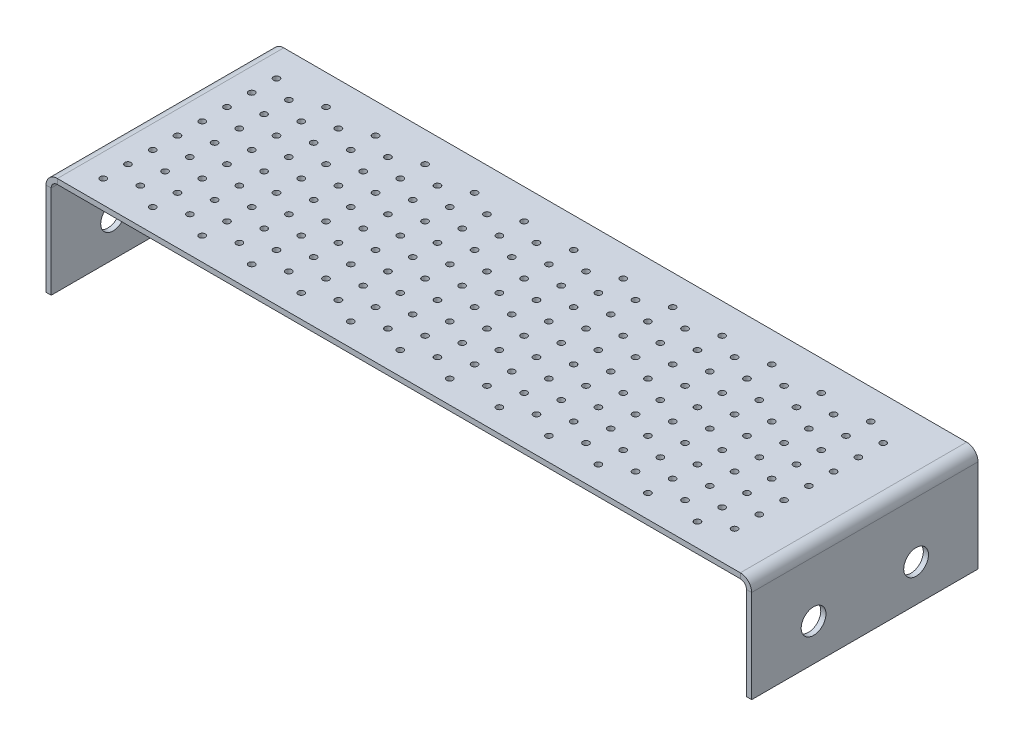
SolidWorks part; units mm, degrees
note: The reader was unsure of these and kept them because the rebuilt part matched: flange length of "Edge-Flange1", "Edge-Flange2".
material "Plain Carbon Steel"
ref_plane "Front Plane" through (0, 0, 0) normal (0, 0, 1) x (1, 0, 0)
ref_plane "Top Plane" through (0, 0, 0) normal (0, 1, 0) x (1, 0, 0)
ref_plane "Right Plane" through (0, 0, 0) normal (1, 0, 0) x (0, 0, -1)
sketch "Sketch1" plane through (0, 0, 0) normal (0, 1, 0) x (1, 0, 0)
  line L1 (0, 0) -> (361.95, 0)
  line L2 (0, 0) -> (0, 116.0882)
  line L3 (0, 116.0882) -> (361.95, 116.0882)
  line L4 (361.95, 0) -> (361.95, 116.0882)
  dimension "D1" = 361.95
  dimension "D2" = 116.0882
base flange "Base-Flange1" sketch "Sketch1" thickness 2.6568 reverse thickness direction no parameters "D1"=3.175
edge flange "Edge-Flange1" sketch "Sketch8" flange angle 90 flange length 50.8 flange position material inside bend radius 3.175 thickness 2.6568 relief rectangular parameters "D6"=10
sketch "Sketch8" plane through (361.95, -2.6568, 0) normal (-1, 0, 0) x (0, 0, -1)
  line L2 (0, 0) -> (0, 50.8)
  line L3 (0, 50.8) -> (116.0882, 50.8)
  line L4 (116.0882, 50.8) -> (116.0882, 0)
  line L5 (116.0882, 0) -> (0, 0) construction
  line L6 (116.0882, 0) -> (0, 0)
bend "EdgeBend1" bend radius 3.175 bend angle 90 parameters "D5"=1
edge flange "Edge-Flange2" sketch "Sketch11" flange angle 90 flange length 50.8 flange position material inside bend radius 3.175 thickness 2.6568 relief rectangular parameters "D6"=10
sketch "Sketch11" plane through (0, -2.6568, 0) normal (1, 0, 0) x (0, 0, 1)
  line L2 (-116.0882, 0) -> (-116.0882, 50.8)
  line L3 (-116.0882, 50.8) -> (0, 50.8)
  line L4 (0, 50.8) -> (0, 0)
  line L5 (0, 0) -> (-116.0882, 0) construction
  line L6 (0, 0) -> (-116.0882, 0)
bend "EdgeBend2" bend radius 3.175 bend angle 90 parameters "D5"=2
sketch "Sketch12" plane through (0, 0, 0) normal (0, 1, 0) x (1, 0, 0)
  line L0 (5.8318, 116.0882) -> (5.8318, 0) construction
  line L1 (15.9918, 105.9282) -> (345.9582, 105.9282) construction
  line L2 (15.9918, 105.9282) -> (15.9918, 10.16) construction
  line L3 (15.9918, 10.16) -> (345.9582, 10.16) construction
  line L4 (345.9582, 105.9282) -> (345.9582, 10.16) construction
  line L5 (356.1182, 116.0882) -> (5.8318, 116.0882) construction
  line L6 (5.8318, 0) -> (356.1182, 0) construction
  line L7 (356.1182, 0) -> (356.1182, 116.0882) construction
  line L8 (17.5793, 11.7475) -> (17.5793, 24.4475) construction
  line L9 (17.5793, 11.7475) -> (17.5793, 14.9225) construction
  line L10 (17.5793, 11.7475) -> (42.9793, 11.7475) construction
  line L11 (30.2793, 18.0975) -> (30.2793, 30.7975) construction
  line L12 (30.2793, 43.4975) -> (55.6793, 43.4975) construction
  circle A0 centre (17.5793, 11.7475) radius 1.5875
  circle A1 centre (17.5793, 24.4475) radius 1.5875
  circle A2 centre (17.5793, 37.1475) radius 1.5875
  circle A3 centre (17.5793, 49.8475) radius 1.5875
  circle A4 centre (17.5793, 62.5475) radius 1.5875
  circle A5 centre (17.5793, 75.2475) radius 1.5875
  circle A6 centre (17.5793, 87.9475) radius 1.5875
  circle A7 centre (17.5793, 100.6475) radius 1.5875
  circle A8 centre (42.9793, 11.7475) radius 1.5875
  circle A9 centre (42.9793, 24.4475) radius 1.5875
  circle A10 centre (42.9793, 37.1475) radius 1.5875
  circle A11 centre (42.9793, 49.8475) radius 1.5875
  circle A12 centre (42.9793, 62.5475) radius 1.5875
  circle A13 centre (42.9793, 75.2475) radius 1.5875
  circle A14 centre (42.9793, 87.9475) radius 1.5875
  circle A15 centre (42.9793, 100.6475) radius 1.5875
  circle A16 centre (68.3793, 11.7475) radius 1.5875
  circle A17 centre (68.3793, 24.4475) radius 1.5875
  circle A18 centre (68.3793, 37.1475) radius 1.5875
  circle A19 centre (68.3793, 49.8475) radius 1.5875
  circle A20 centre (68.3793, 62.5475) radius 1.5875
  circle A21 centre (68.3793, 75.2475) radius 1.5875
  circle A22 centre (68.3793, 87.9475) radius 1.5875
  circle A23 centre (68.3793, 100.6475) radius 1.5875
  circle A24 centre (93.7793, 11.7475) radius 1.5875
  circle A25 centre (93.7793, 24.4475) radius 1.5875
  circle A26 centre (93.7793, 37.1475) radius 1.5875
  circle A27 centre (93.7793, 49.8475) radius 1.5875
  circle A28 centre (93.7793, 62.5475) radius 1.5875
  circle A29 centre (93.7793, 75.2475) radius 1.5875
  circle A30 centre (93.7793, 87.9475) radius 1.5875
  circle A31 centre (93.7793, 100.6475) radius 1.5875
  circle A32 centre (119.1793, 11.7475) radius 1.5875
  circle A33 centre (119.1793, 24.4475) radius 1.5875
  circle A34 centre (119.1793, 37.1475) radius 1.5875
  circle A35 centre (119.1793, 49.8475) radius 1.5875
  circle A36 centre (119.1793, 62.5475) radius 1.5875
  circle A37 centre (119.1793, 75.2475) radius 1.5875
  circle A38 centre (119.1793, 87.9475) radius 1.5875
  circle A39 centre (119.1793, 100.6475) radius 1.5875
  circle A40 centre (144.5793, 11.7475) radius 1.5875
  circle A41 centre (144.5793, 24.4475) radius 1.5875
  circle A42 centre (144.5793, 37.1475) radius 1.5875
  circle A43 centre (144.5793, 49.8475) radius 1.5875
  circle A44 centre (144.5793, 62.5475) radius 1.5875
  circle A45 centre (144.5793, 75.2475) radius 1.5875
  circle A46 centre (144.5793, 87.9475) radius 1.5875
  circle A47 centre (144.5793, 100.6475) radius 1.5875
  circle A48 centre (169.9793, 11.7475) radius 1.5875
  circle A49 centre (169.9793, 24.4475) radius 1.5875
  circle A50 centre (169.9793, 37.1475) radius 1.5875
  circle A51 centre (169.9793, 49.8475) radius 1.5875
  circle A52 centre (169.9793, 62.5475) radius 1.5875
  circle A53 centre (169.9793, 75.2475) radius 1.5875
  circle A54 centre (169.9793, 87.9475) radius 1.5875
  circle A55 centre (169.9793, 100.6475) radius 1.5875
  circle A56 centre (195.3793, 11.7475) radius 1.5875
  circle A57 centre (195.3793, 24.4475) radius 1.5875
  circle A58 centre (195.3793, 37.1475) radius 1.5875
  circle A59 centre (195.3793, 49.8475) radius 1.5875
  circle A60 centre (195.3793, 62.5475) radius 1.5875
  circle A61 centre (195.3793, 75.2475) radius 1.5875
  circle A62 centre (195.3793, 87.9475) radius 1.5875
  circle A63 centre (195.3793, 100.6475) radius 1.5875
  circle A64 centre (220.7793, 11.7475) radius 1.5875
  circle A65 centre (220.7793, 24.4475) radius 1.5875
  circle A66 centre (220.7793, 37.1475) radius 1.5875
  circle A67 centre (220.7793, 49.8475) radius 1.5875
  circle A68 centre (220.7793, 62.5475) radius 1.5875
  circle A69 centre (220.7793, 75.2475) radius 1.5875
  circle A70 centre (220.7793, 87.9475) radius 1.5875
  circle A71 centre (220.7793, 100.6475) radius 1.5875
  circle A72 centre (246.1793, 11.7475) radius 1.5875
  circle A73 centre (246.1793, 24.4475) radius 1.5875
  circle A74 centre (246.1793, 37.1475) radius 1.5875
  circle A75 centre (246.1793, 49.8475) radius 1.5875
  circle A76 centre (246.1793, 62.5475) radius 1.5875
  circle A77 centre (246.1793, 75.2475) radius 1.5875
  circle A78 centre (246.1793, 87.9475) radius 1.5875
  circle A79 centre (246.1793, 100.6475) radius 1.5875
  circle A80 centre (271.5793, 11.7475) radius 1.5875
  circle A81 centre (271.5793, 24.4475) radius 1.5875
  circle A82 centre (271.5793, 37.1475) radius 1.5875
  circle A83 centre (271.5793, 49.8475) radius 1.5875
  circle A84 centre (271.5793, 62.5475) radius 1.5875
  circle A85 centre (271.5793, 75.2475) radius 1.5875
  circle A86 centre (271.5793, 87.9475) radius 1.5875
  circle A87 centre (271.5793, 100.6475) radius 1.5875
  circle A88 centre (296.9793, 11.7475) radius 1.5875
  circle A89 centre (296.9793, 24.4475) radius 1.5875
  circle A90 centre (296.9793, 37.1475) radius 1.5875
  circle A91 centre (296.9793, 49.8475) radius 1.5875
  circle A92 centre (296.9793, 62.5475) radius 1.5875
  circle A93 centre (296.9793, 75.2475) radius 1.5875
  circle A94 centre (296.9793, 87.9475) radius 1.5875
  circle A95 centre (296.9793, 100.6475) radius 1.5875
  circle A96 centre (322.3793, 11.7475) radius 1.5875
  circle A97 centre (322.3793, 24.4475) radius 1.5875
  circle A98 centre (322.3793, 37.1475) radius 1.5875
  circle A99 centre (322.3793, 49.8475) radius 1.5875
  circle A100 centre (322.3793, 62.5475) radius 1.5875
  circle A101 centre (322.3793, 75.2475) radius 1.5875
  circle A102 centre (322.3793, 87.9475) radius 1.5875
  circle A103 centre (322.3793, 100.6475) radius 1.5875
  circle A104 centre (30.2793, 18.0975) radius 1.5875
  circle A105 centre (30.2793, 30.7975) radius 1.5875
  circle A106 centre (30.2793, 43.4975) radius 1.5875
  circle A107 centre (30.2793, 56.1975) radius 1.5875
  circle A108 centre (30.2793, 68.8975) radius 1.5875
  circle A109 centre (30.2793, 81.5975) radius 1.5875
  circle A110 centre (30.2793, 94.2975) radius 1.5875
  circle A111 centre (55.6793, 43.4975) radius 1.5875
  circle A112 centre (55.6793, 56.1975) radius 1.5875
  circle A113 centre (55.6793, 68.8975) radius 1.5875
  circle A114 centre (55.6793, 81.5975) radius 1.5875
  circle A115 centre (55.6793, 94.2975) radius 1.5875
  circle A116 centre (55.6793, 30.7975) radius 1.5875
  circle A117 centre (55.6793, 18.0975) radius 1.5875
  circle A118 centre (81.0793, 43.4975) radius 1.5875
  circle A119 centre (81.0793, 56.1975) radius 1.5875
  circle A120 centre (81.0793, 68.8975) radius 1.5875
  circle A121 centre (81.0793, 81.5975) radius 1.5875
  circle A122 centre (81.0793, 94.2975) radius 1.5875
  circle A123 centre (81.0793, 30.7975) radius 1.5875
  circle A124 centre (81.0793, 18.0975) radius 1.5875
  circle A125 centre (106.4793, 43.4975) radius 1.5875
  circle A126 centre (106.4793, 56.1975) radius 1.5875
  circle A127 centre (106.4793, 68.8975) radius 1.5875
  circle A128 centre (106.4793, 81.5975) radius 1.5875
  circle A129 centre (106.4793, 94.2975) radius 1.5875
  circle A130 centre (106.4793, 30.7975) radius 1.5875
  circle A131 centre (106.4793, 18.0975) radius 1.5875
  circle A132 centre (131.8793, 43.4975) radius 1.5875
  circle A133 centre (131.8793, 56.1975) radius 1.5875
  circle A134 centre (131.8793, 68.8975) radius 1.5875
  circle A135 centre (131.8793, 81.5975) radius 1.5875
  circle A136 centre (131.8793, 94.2975) radius 1.5875
  circle A137 centre (131.8793, 30.7975) radius 1.5875
  circle A138 centre (131.8793, 18.0975) radius 1.5875
  circle A139 centre (157.2793, 43.4975) radius 1.5875
  circle A140 centre (157.2793, 56.1975) radius 1.5875
  circle A141 centre (157.2793, 68.8975) radius 1.5875
  circle A142 centre (157.2793, 81.5975) radius 1.5875
  circle A143 centre (157.2793, 94.2975) radius 1.5875
  circle A144 centre (157.2793, 30.7975) radius 1.5875
  circle A145 centre (157.2793, 18.0975) radius 1.5875
  circle A146 centre (182.6793, 43.4975) radius 1.5875
  circle A147 centre (182.6793, 56.1975) radius 1.5875
  circle A148 centre (182.6793, 68.8975) radius 1.5875
  circle A149 centre (182.6793, 81.5975) radius 1.5875
  circle A150 centre (182.6793, 94.2975) radius 1.5875
  circle A151 centre (182.6793, 30.7975) radius 1.5875
  circle A152 centre (182.6793, 18.0975) radius 1.5875
  circle A153 centre (208.0793, 43.4975) radius 1.5875
  circle A154 centre (208.0793, 56.1975) radius 1.5875
  circle A155 centre (208.0793, 68.8975) radius 1.5875
  circle A156 centre (208.0793, 81.5975) radius 1.5875
  circle A157 centre (208.0793, 94.2975) radius 1.5875
  circle A158 centre (208.0793, 30.7975) radius 1.5875
  circle A159 centre (208.0793, 18.0975) radius 1.5875
  circle A160 centre (233.4793, 43.4975) radius 1.5875
  circle A161 centre (233.4793, 56.1975) radius 1.5875
  circle A162 centre (233.4793, 68.8975) radius 1.5875
  circle A163 centre (233.4793, 81.5975) radius 1.5875
  circle A164 centre (233.4793, 94.2975) radius 1.5875
  circle A165 centre (233.4793, 30.7975) radius 1.5875
  circle A166 centre (233.4793, 18.0975) radius 1.5875
  circle A167 centre (258.8793, 43.4975) radius 1.5875
  circle A168 centre (258.8793, 56.1975) radius 1.5875
  circle A169 centre (258.8793, 68.8975) radius 1.5875
  circle A170 centre (258.8793, 81.5975) radius 1.5875
  circle A171 centre (258.8793, 94.2975) radius 1.5875
  circle A172 centre (258.8793, 30.7975) radius 1.5875
  circle A173 centre (258.8793, 18.0975) radius 1.5875
  circle A174 centre (284.2793, 43.4975) radius 1.5875
  circle A175 centre (284.2793, 56.1975) radius 1.5875
  circle A176 centre (284.2793, 68.8975) radius 1.5875
  circle A177 centre (284.2793, 81.5975) radius 1.5875
  circle A178 centre (284.2793, 94.2975) radius 1.5875
  circle A179 centre (284.2793, 30.7975) radius 1.5875
  circle A180 centre (284.2793, 18.0975) radius 1.5875
  circle A181 centre (309.6793, 43.4975) radius 1.5875
  circle A182 centre (309.6793, 56.1975) radius 1.5875
  circle A183 centre (309.6793, 68.8975) radius 1.5875
  circle A184 centre (309.6793, 81.5975) radius 1.5875
  circle A185 centre (309.6793, 94.2975) radius 1.5875
  circle A186 centre (309.6793, 30.7975) radius 1.5875
  circle A187 centre (309.6793, 18.0975) radius 1.5875
  circle A188 centre (335.0793, 43.4975) radius 1.5875
  circle A189 centre (335.0793, 56.1975) radius 1.5875
  circle A190 centre (335.0793, 68.8975) radius 1.5875
  circle A191 centre (335.0793, 81.5975) radius 1.5875
  circle A192 centre (335.0793, 94.2975) radius 1.5875
  circle A193 centre (335.0793, 30.7975) radius 1.5875
  circle A194 centre (335.0793, 18.0975) radius 1.5875
  dimension "D5" = 3.175
  dimension "D10" = 3.175
  dimension "D1" = 10.16
  dimension "D2" = 10.16
  dimension "D3" = 10.16
  dimension "D4" = 10.16
  dimension "D7" = 12.7
  dimension "D8" = 13
  dimension "D9" = 25.4
  dimension "D12" = 12.7
  dimension "D11" = 6.35
  dimension "D14" = 12.7
  dimension "D16" = 25.4
  dimension "D6" = 8
  dimension "D13" = 7
  dimension "D15" = 13
extrude "Cut-Extrude1" cut sketch "Sketch12" against normal through all normal cut yes
sketch "Sketch13" plane through (361.95, 0, 0) normal (1, 0, 0) x (0, 0, -1)
  line L0 (0, -53.4568) -> (0, -5.8318) construction
  line L1 (116.0882, -5.8318) -> (116.0882, -53.4568) construction
  line L3 (116.0882, -53.4568) -> (0, -53.4568) construction
  circle A0 centre (31.75, -34.4068) radius 6.35
  circle A1 centre (84.3382, -34.4068) radius 6.35
  dimension "D1" = 12.7
  dimension "D2" = 31.75
  dimension "D3" = 31.75
  dimension "D4" = 19.05
  dimension "D5" = 19.05
extrude "Cut-Extrude2" cut sketch "Sketch13" against normal through all both and the other way through all normal cut yes
sketch "Bend-Lines1" [suppressed] plane through (0, 0, 0) normal (0, 1, 0) x (1, 0, 0)
sketch "Bounding-Box1" [suppressed] plane through (0, 0, 0) normal (0, 1, 0) x (1, 0, 0)
sheet metal parameters "Sheet-Metal1" thickness 2.6568 parameters "D1"=3.175
flat pattern "Flat-Pattern1" [suppressed]
sketch "Bend-Lines2" plane through (0, 0, 0) normal (0, 1, 0) x (1, 0, 0)
sketch3d "Bounding-Box2" [suppressed]
  line L0 (-361.95, 119.6975, 0) -> (0, 119.6975, 0) construction
  line L1 (-361.95, 0, 0) -> (0, 0, 0) construction
  line L2 (-361.95, 119.6975, 0) -> (-361.95, 0, 0) construction
  line L3 (0, 119.6975, 0) -> (0, 0, 0) construction
sheet metal parameters "Sheet-Metal2" thickness 2.6568 parameters "D1"=3.175
flat pattern "Flat-Pattern1"
sketch "Bend-Lines2" plane through (0, 0, 0) normal (0, 1, 0) x (1, 0, 0)
  line L0 (359.6551, 0) -> (359.6551, 119.6975) construction
  line L1 (359.6551, 0) -> (359.6551, 119.6975) construction
sketch3d "Bounding-Box2" [suppressed]
  line L0 (410.8171, 119.6975, 0) -> (0, 119.6975, 0) construction
  line L1 (410.8171, 0, 0) -> (0, 0, 0) construction
  line L2 (410.8171, 119.6975, 0) -> (410.8171, 0, 0) construction
  line L3 (0, 119.6975, 0) -> (0, 0, 0) construction
bend of the flat pattern "Flatten-<EdgeBend1>1"
sheet metal parameters "Sheet-Metal3" thickness 2.6568 parameters "D1"=3.175
flat pattern "Flat-Pattern1"
sketch "Bend-Lines2" plane through (0, 0, 0) normal (0, 1, 0) x (1, 0, 0)
  line L0 (359.6551, 0) -> (359.6551, 119.38) construction
  line L1 (359.6551, 0) -> (359.6551, 119.38) construction
  line L2 (2.2949, 119.38) -> (2.2949, 0) construction
  line L3 (2.2949, 119.38) -> (2.2949, 0) construction
sketch3d "Bounding-Box2" [suppressed]
  line L0 (410.8171, 119.38, 0) -> (-48.8671, 119.38, 0) construction
  line L1 (410.8171, 0, 0) -> (-48.8671, 0, 0) construction
  line L2 (410.8171, 119.38, 0) -> (410.8171, 0, 0) construction
  line L3 (-48.8671, 119.38, 0) -> (-48.8671, 0, 0) construction
bend of the flat pattern "Flatten-<EdgeBend1>1"
bend of the flat pattern "Flatten-<EdgeBend2>1"
sheet metal parameters "Sheet-Metal4" thickness 2.6568 parameters "D1"=3.175
flat pattern "Flat-Pattern1" [suppressed]
sketch "Bend-Lines2" plane through (0, 0, 0) normal (0, 1, 0) x (1, 0, 0)
  line L0 (359.6551, 0) -> (359.6551, 119.38) construction
  line L1 (359.6551, 0) -> (359.6551, 119.38) construction
  line L2 (2.2949, 119.38) -> (2.2949, 0) construction
  line L3 (2.2949, 119.38) -> (2.2949, 0) construction
sketch3d "Bounding-Box2" [suppressed]
  line L0 (410.8171, 119.38, 0) -> (-48.8671, 119.38, 0) construction
  line L1 (410.8171, 0, 0) -> (-48.8671, 0, 0) construction
  line L2 (410.8171, 119.38, 0) -> (410.8171, 0, 0) construction
  line L3 (-48.8671, 119.38, 0) -> (-48.8671, 0, 0) construction
bend of the flat pattern "Flatten-<EdgeBend1>1"
bend of the flat pattern "Flatten-<EdgeBend2>1"
sketch "Sketch13-1" [suppressed] plane through (357.3603, -2.6568, 0) normal (0, -1, 0) x (0, 0, 1)
  circle A2 centre (-87.63, -29.6443) radius 6.35
  circle A3 centre (-31.75, -29.6443) radius 6.35
sheet metal parameters "Sheet-Metal6" thickness 2.6568 parameters "D1"=3.175
flat pattern "Flat-Pattern1"
sketch "Bend-Lines2" plane through (0, 0, 0) normal (0, 1, 0) x (1, 0, 0)
  line L0 (359.6551, 0) -> (359.6551, 116.0882) construction
  line L1 (359.6551, 0) -> (359.6551, 116.0882) construction
  line L2 (2.2949, 116.0882) -> (2.2949, 0) construction
  line L3 (2.2949, 116.0882) -> (2.2949, 0) construction
sketch3d "Bounding-Box2" [suppressed]
  line L0 (410.8171, 116.0882, 0) -> (-48.8671, 116.0882, 0) construction
  line L1 (410.8171, 0, 0) -> (-48.8671, 0, 0) construction
  line L2 (410.8171, 116.0882, 0) -> (410.8171, 0, 0) construction
  line L3 (-48.8671, 116.0882, 0) -> (-48.8671, 0, 0) construction
bend of the flat pattern "Flatten-<EdgeBend1>1"
bend of the flat pattern "Flatten-<EdgeBend2>1"
